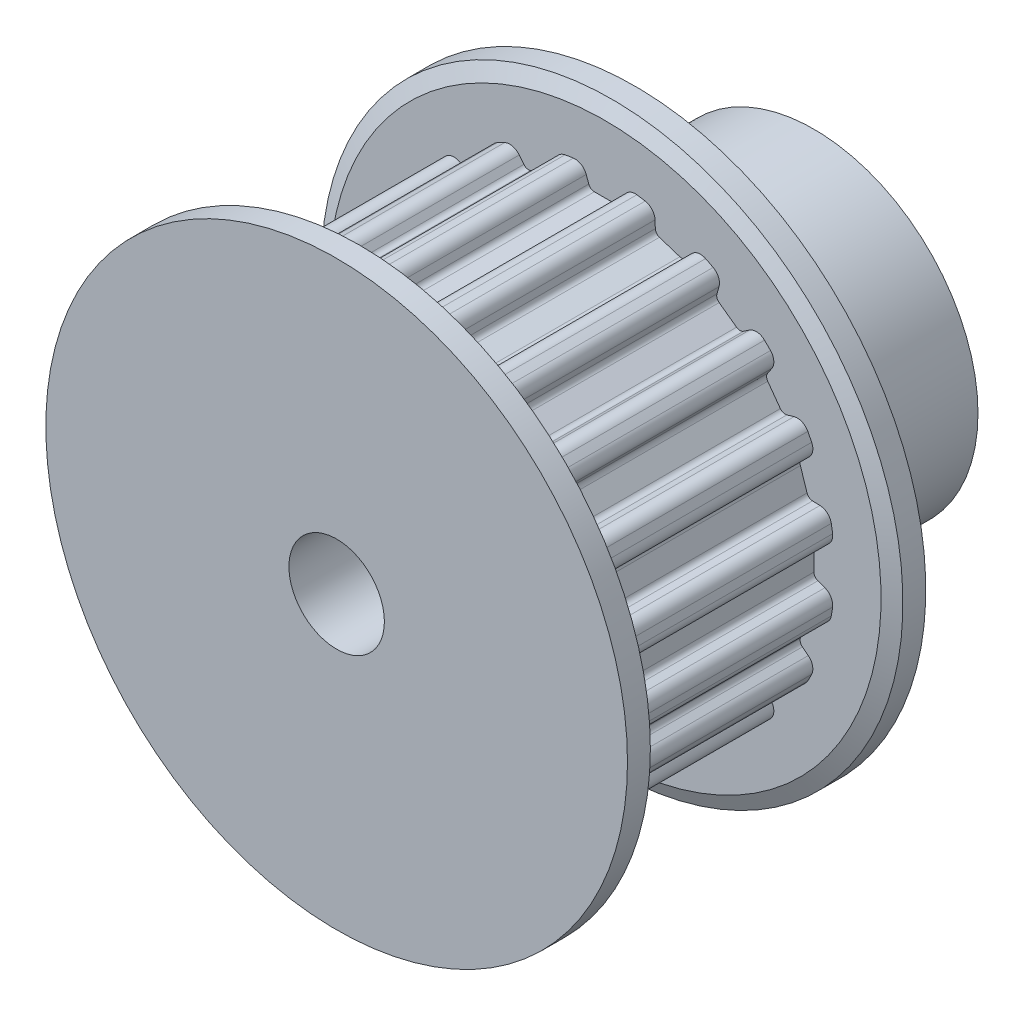
SolidWorks part; units mm, degrees
ref_plane "Front" through (0, 0, 0) normal (0, 0, 1) x (1, 0, 0)
ref_plane "Top" through (0, 0, 0) normal (0, 1, 0) x (1, 0, 0)
ref_plane "Right" through (0, 0, 0) normal (1, 0, 0) x (0, 0, -1)
sketch "support-front-body" plane through (0, 0, 0) normal (0, 0, 1) x (1, 0, 0)
  line L0 (0, 0) -> (0, 7.7) construction
  line L1 (0, 0) -> (0, -7.7) construction
  line L2 (0, 0) -> (7.7, 0) construction
  line L3 (0, 0) -> (-7.7, 0) construction
  circle A0 centre (0, 0) radius 7.7
  dimension "diam-outer" = 15.4
sketch "support-right-body" plane through (0, 0, 0) normal (1, 0, 0) x (0, 0, -1)
  line L0 (0, 0) -> (10, 0) construction
  line L1 (0, 7.7) -> (10, 7.7)
  line L2 (0, 7.7) -> (0, -7.7)
  line L3 (0, -7.7) -> (10, -7.7)
  line L4 (10, 7.7) -> (10, -7.7)
  dimension "length" = 10
sketch "support-right-chamfer" plane through (0, 0, 0) normal (1, 0, 0) x (0, 0, -1)
  line L0 (0, 0) -> (10, 0) construction
  line L1 (0, -7.7) -> (0, -6.7)
  line L2 (0, 7.7) -> (0, -7.7) construction
  line L4 (0, -6.7) -> (1, -7.7)
  line L5 (0, -7.7) -> (10, -7.7) construction
  line L7 (1, -7.7) -> (0, -7.7)
  line L9 (10, -7.7) -> (9, -7.7)
  line L11 (9, -7.7) -> (10, -6.7)
  line L12 (10, 7.7) -> (10, -7.7) construction
  line L14 (10, -6.7) -> (10, -7.7)
  dimension "height-chamfer-front" = 1
  dimension "angle-chamfer-front" = 45
  dimension "angle-chamfer-back" = 45
  dimension "height-chamfer-back" = 1
sketch "support-right-hub" plane through (0, 0, 0) normal (1, 0, 0) x (0, 0, -1)
  line L0 (16, 0) -> (10, 0) construction
  line L1 (10, 5.5) -> (16, 5.5)
  line L2 (10, 5.5) -> (10, -5.5)
  line L3 (10, -5.5) -> (16, -5.5)
  line L4 (16, 5.5) -> (16, -5.5)
  line L6 (0, 0) -> (10, 0) construction
  line L8 (0, 7.7) -> (0, -7.7) construction
  dimension "diam-hub" = 11
  dimension "length-hub" = 6
  dimension "dist-hub" = 10
sketch "support-right-bore" plane through (0, 0, 0) normal (1, 0, 0) x (0, 0, -1)
  line L0 (0, 7.7) -> (0, -7.7) construction
  line L1 (0, 2) -> (16, 2)
  line L2 (0, 2) -> (0, -2)
  line L3 (0, -2) -> (16, -2)
  line L4 (16, 2) -> (16, 0)
  line L5 (16, 0) -> (0, 0) construction
  line L6 (0, 0) -> (10, 0) construction
  line L7 (16, 0) -> (16, -2)
  line L8 (16, -2) -> (16, 2) construction
  dimension "diam-bore" = 4
  dimension "length-bore" = 16
  dimension "angle-bore-bottom" = 180
  dimension "angle-bore" = 90
sketch "support-stop-screw-hole" plane through (0, 0, 0) normal (1, 0, 0) x (0, 0, -1)
  line L1 (6.5667, 11) -> (9.4333, 11)
  line L2 (6.5667, 11) -> (6.5667, -1)
  line L3 (8, -1) -> (9.4333, -1)
  line L4 (9.4333, 11) -> (9.4333, -1)
  line L5 (8, -1) -> (8, 11) construction
  line L6 (8, -1) -> (6.5667, -1)
  line L7 (0, 0) -> (8, 0) construction
  line L8 (0, 7.7) -> (0, -7.7) construction
  dimension "diam-stop-screw-hole" = 2.8665
  dimension "dist-stop-screw-hole" = 8
  dimension "depth-stop-screw-hole" = 12
  dimension "angle-stop-screw-hole" = 180
  dimension "height-stop-screw-hole" = 11
sketch "support-front-keygroove" plane through (0, 0, 0) normal (0, 0, 1) x (1, 0, 0)
  line L0 (0, 0) -> (0, -2) construction
  line L1 (-1, 6) -> (1, 6)
  line L2 (-1, 6) -> (-1, 3.8)
  line L3 (-1, 3.8) -> (1, 3.8)
  line L4 (1, 6) -> (1, 3.8)
  line L5 (0, 0) -> (0, 2) construction
  circle A0 centre (0, 0) radius 2 construction
  dimension "width-keygroove" = 2
  dimension "dist-keygroove" = 8
  dimension "height-keygroove" = 2.2
sketch "support-front-tooth" plane through (0, 0, 0) normal (0, 0, 1) x (1, 0, 0)
  line L0 (0.5479, 7.1316) -> (0.6335, 7.3667)
  line L1 (0, 0) -> (0, 7.7) construction
  line L2 (-0.5479, 7.1316) -> (-0.6335, 7.3667)
  line L3 (-0.36, 7) -> (0.36, 7)
  line L4 (0, 7) -> (-1.0646, 7.626) construction
  line L5 (0, 7) -> (-0.5479, 7.1316) construction
  line L6 (0, 7.7) -> (0.5704, 7.6062) construction
  line L7 (0, 7.7) -> (2.4668, 7.2942) construction
  line L8 (0, 7.626) -> (0, 7) construction
  line L9 (1.0646, 7.626) -> (-1.0646, 7.626) construction
  line L10 (0, 7.626) -> (0, 8.2521) construction
  line L11 (0, 0) -> (1.2334, 7.4971) construction
  line L12 (1.4346, 7.5652) -> (1.6352, 8.1582)
  line L13 (1.6352, 8.1582) -> (3.6522, 7.4761)
  line L14 (3.6522, 7.4761) -> (3.4517, 6.883)
  line L15 (2.5836, 6.5157) -> (2.9601, 6.7755)
  line L16 (2.5836, 6.5157) -> (1.9016, 6.7464)
  line L17 (1.0646, 7.626) -> (1.0646, 8.2521)
  line L21 (-1.0646, 8.2521) -> (-1.0646, 7.626)
  line L22 (1.0646, 8.2521) -> (-1.0646, 8.2521)
  line L23 (1.9016, 6.7464) -> (1.76, 7.1814)
  line L24 (1.4346, 7.5652) -> (1.0646, 7.626) construction
  line L25 (-0.5479, 7.1316) -> (-0.5, 7) construction
  line L26 (-0.5, 7) -> (0.5, 7) construction
  line L27 (0.5, 7) -> (0.5479, 7.1316) construction
  line L28 (0.5704, 7.6062) -> (1.0093, 7.2299) construction
  arc A0 (-0.5479, 7.1316) -> (-0.36, 7) centre (-0.36, 7.2) ccw
  circle A1 centre (0, 0) radius 7.7 construction
  arc A2 (0.6335, 7.3667) -> (1.0646, 7.626) centre (1.0093, 7.2299) cw
  arc A3 (-0.6335, 7.3667) -> (-1.0646, 7.626) centre (-1.0093, 7.2299) ccw
  arc A4 (0.5479, 7.1316) -> (0.36, 7) centre (0.36, 7.2) cw
  circle A5 centre (0, 0) radius 7.7 construction
  arc A6 (1.76, 7.1814) -> (1.4346, 7.5652) centre (1.3601, 7.1722) ccw
  arc A7 (2.9601, 6.7755) -> (3.4517, 6.883) centre (3.2724, 6.5255) cw
  dimension "D3" = 0.4
  dimension "D2" = 40
  dimension "D1" = 0.2
  dimension "D4" = 1
  dimension "height-tooth" = 0.7
  dimension "pitch" = 2.5
sketch "support-right-flange" plane through (0, 0, 0) normal (1, 0, 0) x (0, 0, -1)
  line L0 (0, 4.85) -> (0, 8.1167)
  line L1 (10, 7.7) -> (10, -7.7) construction
  line L2 (0, 8.1167) -> (1, 8.1167) construction
  line L3 (1, 8.1167) -> (1, 9.75)
  line L4 (0, 9.75) -> (1, 9.75)
  line L5 (1, 8.1167) -> (1, 4.85)
  line L6 (1, 4.85) -> (0, 4.85)
  line L7 (5, 7.7) -> (5, 0) construction
  line L8 (0, 7.7) -> (10, 7.7) construction
  line L9 (0, 8.1167) -> (0, 9.75)
  line L10 (9, 4.85) -> (10, 4.85)
  line L11 (9, 8.1167) -> (9, 4.85)
  line L12 (10, 9.75) -> (9, 9.75)
  line L13 (9, 8.1167) -> (9, 9.75)
  line L14 (10, 8.1167) -> (10, 9.75)
  line L15 (10, 4.85) -> (10, 8.1167)
  line L16 (10, 0) -> (0, 0) construction
  line L17 (10, -4.85) -> (10, -8.1167)
  line L18 (10, -8.1167) -> (10, -9.75)
  line L19 (9, -8.1167) -> (9, -9.75)
  line L20 (10, -9.75) -> (9, -9.75)
  line L21 (9, -8.1167) -> (9, -4.85)
  line L22 (9, -4.85) -> (10, -4.85)
  line L23 (1, -4.85) -> (0, -4.85)
  line L24 (1, -8.1167) -> (1, -4.85)
  line L25 (0, -9.75) -> (1, -9.75)
  line L26 (1, -8.1167) -> (1, -9.75)
  line L27 (0, -8.1167) -> (0, -9.75)
  line L28 (0, -4.85) -> (0, -8.1167)
  line L29 (0, 0) -> (10, 0) construction
  line L30 (0, 8.1167) -> (1, 8.1167) construction
  line L31 (0.5, 4.85) -> (0.5, 6.4833) construction
  line L32 (0.5, 6.4833) -> (0.5, 8.1167) construction
  line L33 (0.5, 9.75) -> (0.5, 8.1167) construction
  line L34 (0, 7.7) -> (10, 7.7) construction
  dimension "angle-flange" = 180
  dimension "thickness-flange" = 1
  dimension "diam-flange-inner" = 9.7
  dimension "diam-flange-outer" = 19.5
  dimension "width-flange-inner" = 8
sketch "support-right-flange-profile" plane through (0, 0, 0) normal (1, 0, 0) x (0, 0, -1)
  line L0 (0.7668, 9.75) -> (1, 9.75)
  line L2 (1, 9.75) -> (1, 9.25)
  line L3 (1, 8.1167) -> (1, 4.85) construction
  line L4 (1, 9.25) -> (0.7668, 9.75)
  line L5 (0, 0) -> (10, 0) construction
  line L6 (5, 0) -> (5, 7.7) construction
  line L7 (9, 9.25) -> (9.2332, 9.75)
  line L8 (9, 9.75) -> (9, 9.25)
  line L9 (9.2332, 9.75) -> (9, 9.75)
  dimension "D1" = 25
  dimension "D2" = 0.5
ref_axis "ref-axis-center" through (0, 0, -10) along (0, 0, 1)
ref_plane "ref-plane-front" through (0, 0, 0) normal (0, 0, 1) x (1, 0, 0)
ref_plane "ref-plane-back" through (0, 0, -10) normal (0, 0, 1) x (1, 0, 0)
ref_plane "ref-plane-hub-front" through (0, 0, -10) normal (0, 0, 1) x (1, 0, 0)
ref_plane "ref-plane-hub-back" through (0, 0, -16) normal (0, 0, 1) x (1, 0, 0)
ref_plane "ref-plane-bore-front" through (0, 0, 0) normal (0, 0, 1) x (1, 0, 0)
ref_plane "ref-plane-bore-back" through (0, 0, -16) normal (0, 0, 1) x (1, 0, 0)
ref_plane "ref-plane-stop-screw-hole-top" through (0, 11, 0) normal (0, 1, 0) x (-1, 0, 0)
ref_axis "ref-axis-stop-screw-hole" through (0, 11, -8) along (0, -1, 0)
sketch "Sketch5" plane through (0, 0, 0) normal (1, 0, 0) x (0, 0, -1)
  line L0 (10, 7.7) -> (10, -7.7) construction
  line L1 (0, 7.7) -> (10, 7.7) construction
  line L2 (0, 7.7) -> (0, -7.7) construction
  line L3 (0, 0) -> (10, 0) construction
  line L4 (10, 7.7) -> (10, 0)
  line L5 (0, 7.7) -> (10, 7.7)
  line L6 (0, 7.7) -> (0, 0)
  line L7 (0, 0) -> (10, 0) construction
  line L8 (0, 0) -> (10, 0)
  dimension "D1" = 10
  dimension "D2" = 7.7
revolve "body" add sketch "Sketch5" angle 360 about L7
sketch "Sketch11" plane through (0, 0, 0) normal (1, 0, 0) x (0, 0, -1)
  line L0 (0, -7.7) -> (0, -6.7) construction
  line L3 (1, -7.7) -> (0, -7.7) construction
  line L5 (0, -6.7) -> (1, -7.7) construction
  line L8 (0, -7.7) -> (0, -6.7)
  line L9 (1, -7.7) -> (0, -7.7)
  line L10 (0, -6.7) -> (1, -7.7)
  line L11 (0, 0) -> (10, 0) construction
  line L12 (0, 0) -> (10, 0) construction
revolve "cut-chamfer-front" [suppressed] cut sketch "Sketch11" angle 360 about L12
sketch "Sketch13" plane through (0, 0, 0) normal (1, 0, 0) x (0, 0, -1)
  line L0 (0, 0) -> (10, 0) construction
  line L1 (10, -7.7) -> (9, -7.7) construction
  line L2 (10, -6.7) -> (10, -7.7) construction
  line L3 (9, -7.7) -> (10, -6.7) construction
  line L4 (0, 0) -> (10, 0) construction
  line L5 (10, -7.7) -> (9, -7.7)
  line L6 (10, -6.7) -> (10, -7.7)
  line L7 (9, -7.7) -> (10, -6.7)
revolve "cut-chamfer-back" [suppressed] cut sketch "Sketch13" angle 360 about L4
sketch "Sketch16" plane through (0, 0, 0) normal (1, 0, 0) x (0, 0, -1)
  line L0 (16, 5.5) -> (16, -5.5) construction
  line L1 (10, 5.5) -> (16, 5.5) construction
  line L2 (16, 0) -> (10, 0) construction
  line L3 (10, 5.5) -> (10, -5.5) construction
  line L4 (16, 5.5) -> (16, 0)
  line L5 (10, 5.5) -> (16, 5.5)
  line L6 (16, 0) -> (10, 0) construction
  line L7 (10, 5.5) -> (10, 0)
  line L8 (16, 0) -> (10, 0)
revolve "body-hub" add sketch "Sketch16" angle 360 about L6
sketch "Sketch17" plane through (0, 0, 0) normal (1, 0, 0) x (0, 0, -1)
  line L0 (16, 2) -> (16, 0) construction
  line L1 (16, 0) -> (0, 0) construction
  line L2 (0, 2) -> (16, 2) construction
  line L3 (0, 2) -> (0, -2) construction
  line L4 (16, 2) -> (16, 0)
  line L5 (16, 0) -> (0, 0) construction
  line L6 (0, 2) -> (16, 2)
  line L7 (0, 2) -> (0, 0)
  line L8 (16, 0) -> (0, 0)
  dimension "D1" = 2
revolve "body-bore" cut sketch "Sketch17" angle 360 about L5
sketch "Sketch19" plane through (0, 0, 0) normal (1, 0, 0) x (0, 0, -1)
  line L0 (6.5667, 11) -> (9.4333, 11) construction
  line L1 (8, -1) -> (8, 11) construction
  line L2 (9.4333, 11) -> (9.4333, -1) construction
  line L3 (8, -1) -> (9.4333, -1) construction
  line L4 (8, 11) -> (9.4333, 11)
  line L5 (8, -1) -> (8, 11) construction
  line L6 (9.4333, 11) -> (9.4333, -1)
  line L7 (8, -1) -> (9.4333, -1)
  line L8 (8, -1) -> (8, 11)
revolve "body-stop-screw-hole" [suppressed] cut sketch "Sketch19" angle 360 about L5
pattern_circular "pattern-stop-screw-hole" [suppressed] count 2 every 90 about axis through (0, 0, -10) along (0, 0, 1) reverse direction yes
sketch "Sketch21" plane through (0, 0, 0) normal (0, 0, 1) x (1, 0, 0)
  line L0 (-1, 6) -> (1, 6) construction
  line L1 (-1, 6) -> (-1, 3.8) construction
  line L2 (-1, 3.8) -> (1, 3.8) construction
  line L3 (1, 6) -> (1, 3.8) construction
  line L4 (-1, 6) -> (1, 6)
  line L5 (-1, 6) -> (-1, 3.8)
  line L6 (-1, 3.8) -> (1, 3.8)
  line L7 (1, 6) -> (1, 3.8)
extrude "cut-keygroove" [suppressed] cut sketch "Sketch21" against normal up to surface (17.5 mm away) up to plane "ref-plane-bore-back"
sketch "Sketch23" plane through (0, 0, 0) normal (0, 0, 1) x (1, 0, 0)
  line L0 (0.5479, 7.1316) -> (0.6335, 7.3667) construction
  line L1 (-0.5479, 7.1316) -> (-0.6335, 7.3667) construction
  line L2 (-1.0646, 8.2521) -> (-1.0646, 7.626) construction
  line L3 (1.0646, 8.2521) -> (-1.0646, 8.2521) construction
  line L4 (1.0646, 7.626) -> (1.0646, 8.2521) construction
  line L6 (0.5479, 7.1316) -> (0.6335, 7.3667)
  line L7 (-0.5479, 7.1316) -> (-0.6335, 7.3667)
  line L8 (-1.0646, 8.2521) -> (-1.0646, 7.626)
  line L9 (1.0646, 8.2521) -> (-1.0646, 8.2521)
  line L10 (1.0646, 7.626) -> (1.0646, 8.2521)
  line L11 (-0.36, 7) -> (0.36, 7) construction
  line L12 (-0.36, 7) -> (0.36, 7)
  arc A0 (0.36, 7) -> (0.5479, 7.1316) centre (0.36, 7.2) ccw construction
  arc A1 (-0.5479, 7.1316) -> (-0.36, 7) centre (-0.36, 7.2) ccw construction
  arc A2 (-0.6335, 7.3667) -> (-1.0646, 7.626) centre (-1.0093, 7.2299) ccw construction
  arc A3 (1.0646, 7.626) -> (0.6335, 7.3667) centre (1.0093, 7.2299) ccw construction
  arc A4 (0.36, 7) -> (0.5479, 7.1316) centre (0.36, 7.2) ccw
  arc A5 (-0.5479, 7.1316) -> (-0.36, 7) centre (-0.36, 7.2) ccw
  arc A6 (-0.6335, 7.3667) -> (-1.0646, 7.626) centre (-1.0093, 7.2299) ccw
  arc A7 (1.0646, 7.626) -> (0.6335, 7.3667) centre (1.0093, 7.2299) ccw
extrude "cut-tooth" cut sketch "Sketch23" against normal up to surface (10 mm away) up to plane "ref-plane-back"
pattern_circular "pattern-tooth" count 20 over 360 about axis through (0, 0, -10) along (0, 0, 1) of "cut-tooth"
sketch "Sketch25" plane through (0, 0, 0) normal (1, 0, 0) x (0, 0, -1)
  line L0 (0, 0) -> (10, 0) construction
  line L1 (1, 4.85) -> (0, 4.85) construction
  line L2 (1, 8.1167) -> (1, 4.85) construction
  line L4 (0, 9.75) -> (1, 9.75) construction
  line L5 (0, 8.1167) -> (0, 9.75) construction
  line L6 (0, 4.85) -> (0, 8.1167) construction
  line L7 (0, 0) -> (10, 0) construction
  line L8 (1, 4.85) -> (0, 4.85)
  line L9 (1, 8.1167) -> (1, 4.85)
  line L10 (0, 9.75) -> (1, 9.75)
  line L11 (1, 8.1167) -> (1, 9.75) construction
  line L12 (0, 8.1167) -> (0, 9.75)
  line L13 (0, 4.85) -> (0, 8.1167)
  line L14 (1, 8.1167) -> (1, 9.75)
revolve "body-flange-front" add sketch "Sketch25" angle 360 about L7
sketch "Sketch26" plane through (0, 0, 0) normal (1, 0, 0) x (0, 0, -1)
  line L0 (10, 0) -> (0, 0) construction
  line L1 (9, 4.85) -> (10, 4.85) construction
  line L2 (9, 8.1167) -> (9, 4.85) construction
  line L4 (10, 9.75) -> (9, 9.75) construction
  line L5 (10, 8.1167) -> (10, 9.75) construction
  line L6 (10, 4.85) -> (10, 8.1167) construction
  line L7 (10, 0) -> (0, 0) construction
  line L8 (9, 4.85) -> (10, 4.85)
  line L9 (9, 8.1167) -> (9, 4.85)
  line L10 (10, 9.75) -> (9, 9.75)
  line L11 (9, 8.1167) -> (9, 9.75) construction
  line L12 (10, 8.1167) -> (10, 9.75)
  line L13 (10, 4.85) -> (10, 8.1167)
  line L14 (9, 8.1167) -> (9, 9.75)
revolve "body-flange-back" add sketch "Sketch26" angle 360 about L7
sketch "Sketch28" plane through (0, 0, 0) normal (1, 0, 0) x (0, 0, -1)
  line L0 (1, 9.75) -> (1, 9.25) construction
  line L1 (0.7668, 9.75) -> (1, 9.75) construction
  line L2 (1, 9.25) -> (0.7668, 9.75) construction
  line L3 (1, 9.75) -> (1, 9.25)
  line L4 (0.7668, 9.75) -> (1, 9.75)
  line L5 (1, 9.25) -> (0.7668, 9.75)
  line L6 (10, 0) -> (0, 0) construction
  line L7 (10, 0) -> (0, 0) construction
revolve "body-flange-profile-front" cut sketch "Sketch28" angle 360 about L7
sketch "Sketch29" plane through (0, 0, 0) normal (1, 0, 0) x (0, 0, -1)
  line L0 (10, 0) -> (0, 0) construction
  line L1 (9, 9.75) -> (9, 9.25) construction
  line L2 (9.2332, 9.75) -> (9, 9.75) construction
  line L3 (9, 9.25) -> (9.2332, 9.75) construction
  line L4 (10, 0) -> (0, 0) construction
  line L5 (9, 9.75) -> (9, 9.25)
  line L6 (9.2332, 9.75) -> (9, 9.75)
  line L7 (9, 9.25) -> (9.2332, 9.75)
revolve "body-flange-profile-back" cut sketch "Sketch29" angle 360 about L4
sketch "support-right-cut-body" plane through (0, 0, 0) normal (1, 0, 0) x (0, 0, -1)
  line L0 (10, 7.7) -> (10, -7.7) construction
  line L1 (0, 7.7) -> (10, 7.7) construction
  line L2 (0, 7.7) -> (0, -7.7) construction
  line L3 (0, -7.7) -> (10, -7.7) construction
  line L4 (10, 7.7) -> (10, -7.7) construction
  line L5 (0, 7.7) -> (0, -7.7) construction
  line L6 (0, 7.7) -> (10, 7.7) construction
  line L7 (0, -7.7) -> (10, -7.7) construction
  line L8 (10, 0) -> (0, 0) construction
  line L9 (5, 7.7) -> (5, -7.7) construction
  line L10 (10, 58.5) -> (6.6667, 58.5)
  line L11 (10, 58.5) -> (10, -58.5)
  line L12 (10, -58.5) -> (6.6667, -58.5)
  line L13 (6.6667, 58.5) -> (6.6667, -58.5)
  line L14 (0, 58.5) -> (3.3333, 58.5)
  line L15 (0, 58.5) -> (0, -58.5)
  line L16 (0, -58.5) -> (3.3333, -58.5)
  line L17 (3.3333, 58.5) -> (3.3333, -58.5)
  line L18 (6.6667, 58.5) -> (3.3333, 58.5) construction
  line L19 (3.3333, -58.5) -> (5, -58.5) construction
  line L21 (10, 5.5) -> (6.6667, 5.5)
  line L23 (10, 5.5) -> (16, 5.5) construction
  line L24 (10, -5.5) -> (6.6667, -5.5)
  line L25 (0, 5.5) -> (3.3333, 5.5)
  line L26 (0, -5.5) -> (3.3333, -5.5)
  dimension "diam" = 117
sketch "support-front-cut-body" plane through (0, 0, 0) normal (0, 0, 1) x (1, 0, 0)
  line L0 (58.5, 0) -> (-58.5, 0) construction
  line L1 (0, 58.5) -> (0, 5.5) construction
  line L2 (0, 7.7) -> (0, -7.7) construction
  line L4 (0, 58.5) -> (-54.972, -20.0082) construction
  line L6 (0, -5.5) -> (0, -58.5) construction
  circle A0 centre (0, 32) radius 15.1998
  circle A1 centre (0, 0) radius 58.5 construction
  circle A2 centre (0, 0) radius 5.5 construction
  dimension "D1" = 35
sketch "Sketch31" plane through (0, 0, 0) normal (1, 0, 0) x (0, 0, -1)
  line L0 (0, 58.5) -> (0, -58.5) construction
  line L1 (0, 58.5) -> (3.3333, 58.5) construction
  line L2 (3.3333, 58.5) -> (3.3333, -58.5) construction
  line L3 (10, 58.5) -> (10, -58.5) construction
  line L4 (10, 58.5) -> (6.6667, 58.5) construction
  line L5 (6.6667, 58.5) -> (6.6667, -58.5) construction
  line L7 (0, 58.5) -> (0, 5.5)
  line L8 (0, 58.5) -> (3.3333, 58.5)
  line L9 (3.3333, 58.5) -> (3.3333, 5.5)
  line L10 (10, 58.5) -> (10, 5.5)
  line L11 (10, 58.5) -> (6.6667, 58.5)
  line L12 (6.6667, 58.5) -> (6.6667, 5.5)
  line L13 (10, 5.5) -> (6.6667, 5.5)
  line L14 (10, 5.5) -> (6.6667, 5.5) construction
  line L15 (3.3333, 5.5) -> (0, 5.5)
  line L16 (0, 0) -> (10, 0) construction
  line L17 (10, 0) -> (0, 0) construction
revolve "cut-body" [suppressed] cut sketch "Sketch31" angle 360 about L16
sketch "Sketch33" plane through (0, 0, 0) normal (0, 0, 1) x (1, 0, 0)
  circle A0 centre (0, 32) radius 15.1998 construction
  circle A1 centre (0, 32) radius 15.1998
extrude "cut-front-body" [suppressed] cut sketch "Sketch33" against normal through all
pattern_circular "pattern-cut-front-body" [suppressed] count 6 over 360 about axis through (0, 0, -10) along (0, 0, 1)
sketch "草图1" plane through (0, 0, -1) normal (0, 0, -1) x (-1, 0, 0)
  circle A0 centre (0, 0) radius 7.7
sketch "草图2" plane through (0, 0, -16) normal (0, 0, -1) x (-1, 0, 0)
  circle A0 centre (0, 0) radius 2.9
  dimension "D1" = 5.8
extrude "切除-拉伸1" cut sketch "草图2" against normal blind 10
sketch "草图3" plane through (0, 0, 0) normal (0, 0, 1) x (1, 0, 0)
  circle A0 centre (0, 0) radius 2.877
  circle A1 centre (0, 0) radius 1.6
  dimension "D1" = 3.2
extrude "凸台-拉伸1" add sketch "草图3" against normal blind 7
